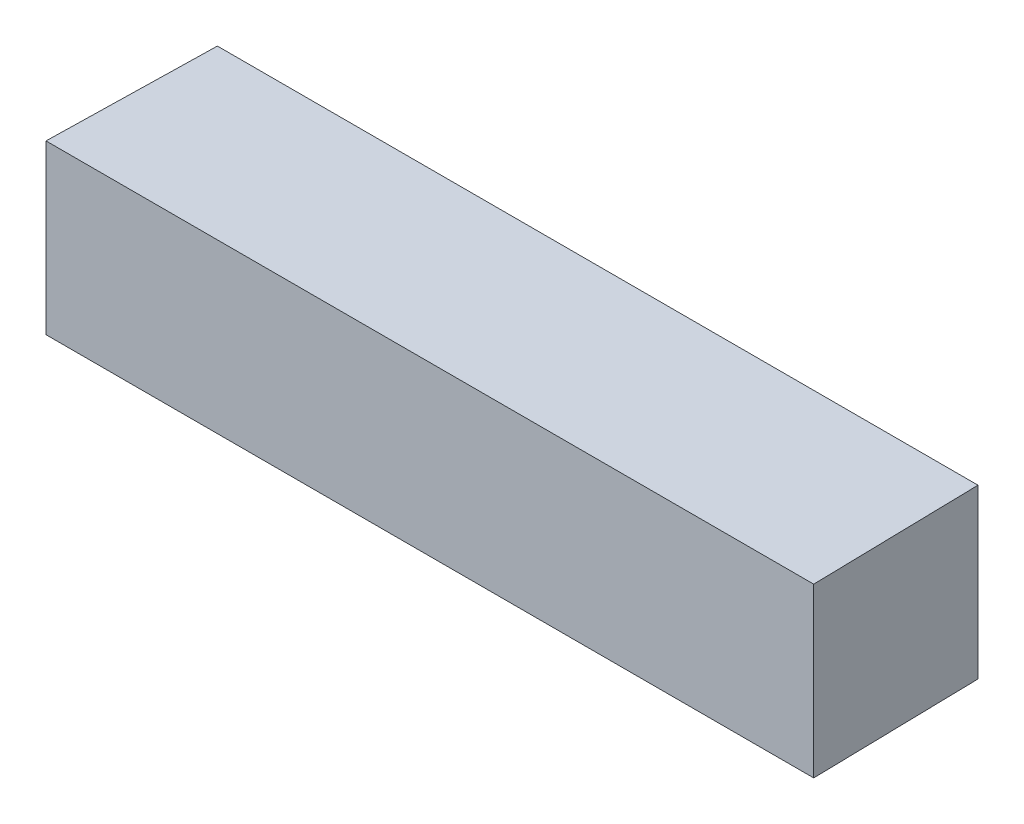
SolidWorks part; units mm, degrees
ref_plane "Front Plane" through (0, 0, 0) normal (0, 0, 1) x (1, 0, 0)
ref_plane "Top Plane" through (0, 0, 0) normal (0, 1, 0) x (1, 0, 0)
ref_plane "Right Plane" through (0, 0, 0) normal (1, 0, 0) x (0, 0, -1)
sketch "Sketch1" plane through (0, 0, 0) normal (0, 1, 0) x (1, 0, 0)
  line L0 (-45.74, 0) -> (-45.3158, 20)
  line L1 (-45.3158, 20) -> (45.3158, 20)
  line L2 (45.3158, 20) -> (45.74, 0)
  line L3 (45.74, 0) -> (-45.74, 0)
  point P4 (0, 0)
  point P7 (0, 20)
  dimension "D1" = 20
  dimension "D2" = 91.48
  dimension "D3" = 2.43
extrude "Boss-Extrude1" add sketch "Sketch1" along normal blind 20
